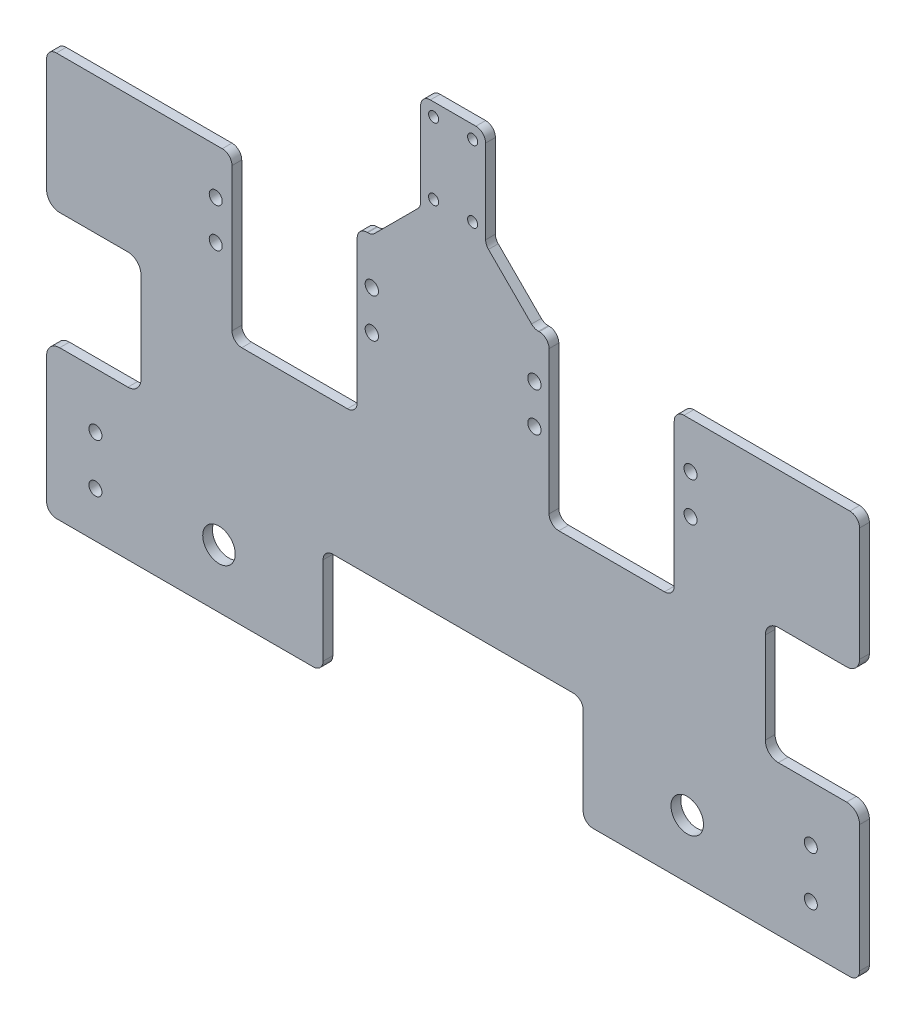
SolidWorks part; units mm, degrees
material "Thornel Mat VMA"
ref_plane "前视基准面" through (0, 0, 0) normal (0, 0, 1) x (1, 0, 0)
ref_plane "上视基准面" through (0, 0, 0) normal (0, 1, 0) x (1, 0, 0)
ref_plane "右视基准面" through (0, 0, 0) normal (1, 0, 0) x (0, 0, -1)
other "Configuration Table"
sketch "草图1" plane through (0, 0, 0) normal (0, 0, 1) x (1, 0, 0)
  line L0 (-32.5, 40) -> (-25, 40)
  line L1 (-25, 40) -> (-10, 55)
  line L2 (-10, 55) -> (-10, 85)
  line L3 (-10, 85) -> (10, 85)
  line L4 (-32.5, 40) -> (-32.5, 0)
  line L5 (-32.5, 0) -> (32.5, 0)
  line L6 (0, 0) -> (0, 50.9699) construction
  line L7 (32.5, 40) -> (32.5, 0)
  line L8 (10, 55) -> (10, 85)
  line L9 (25, 40) -> (10, 55)
  line L10 (32.5, 40) -> (25, 40)
  dimension "D1" = 65
  dimension "D2" = 85
  dimension "D3" = 30
  dimension "D4" = 40
  dimension "D5" = 50
  dimension "D6" = 20
extrude "凸台-拉伸1" add sketch "草图1" along normal blind 3
sketch "草图2" plane through (0, 0, 3) normal (0, 0, 1) x (1, 0, 0)
  line L0 (0, 85) -> (0, 65.679) construction
  line L1 (10, 85) -> (-10, 85) construction
  line L2 (-10, 70) -> (13.1812, 70) construction
  line L3 (-10, 85) -> (-10, 55) construction
  circle A0 centre (-6, 81) radius 1.55
  circle A2 centre (-6, 59) radius 1.55
  circle A3 centre (6, 59) radius 1.55
  circle A4 centre (6, 81) radius 1.55
  dimension "D1" = 4
  dimension "D2" = 4
  dimension "D3" = 3.1
extrude "切除-拉伸1" cut sketch "草图2" against normal through all
sketch "草图3" plane through (0, 0, 3) normal (0, 0, 1) x (1, 0, 0)
  line L0 (32.5, 20) -> (-48.6379, 20) construction
  line L1 (32.5, 0) -> (32.5, 40) construction
  line L2 (0, 0) -> (0, 100.1432) construction
  circle A0 centre (-25, 26) radius 2.05
  circle A2 centre (-25, 14) radius 2.05
  circle A3 centre (25, 14) radius 2.05
  circle A4 centre (25, 26) radius 2.05
  dimension "D1" = 12
  dimension "D2" = 50
  dimension "D3" = 4.1
extrude "切除-拉伸2" cut sketch "草图3" against normal through all
sketch "草图4" plane through (0, 0, 3) normal (0, 0, 1) x (1, 0, 0)
  line L0 (32.5, 0) -> (32.5, 40) construction
  line L1 (32.5, 40) -> (29.5, 40)
  line L2 (32.5, 40) -> (32.5, -0.4765)
  line L3 (32.5, -0.4765) -> (29.5, -0.4765)
  line L4 (29.5, 40) -> (29.5, -0.4765)
  line L5 (0, 85) -> (0, -21.7177) construction
  line L6 (10, 85) -> (-10, 85) construction
  line L7 (-29.5, 40) -> (-29.5, -0.4765)
  line L8 (-32.5, -0.4765) -> (-29.5, -0.4765)
  line L9 (-32.5, 40) -> (-32.5, -0.4765)
  line L10 (-32.5, 40) -> (-29.5, 40)
  dimension "D1" = 3
extrude "切除-拉伸3" cut sketch "草图4" against normal blind 10
sketch "草图5" plane through (0, 0, 3) normal (0, 0, 1) x (1, 0, 0)
  line L0 (0, 0) -> (0, -185.4243) construction
  line L1 (-125, -10) -> (125, -10)
  line L2 (0, 0) -> (0, -84)
  line L3 (-125, -84) -> (125, -84)
  line L4 (125, -10) -> (125, -84)
  line L5 (-125, -10) -> (-125, -84)
  line L6 (-68, -10) -> (-68, 40)
  line L7 (125, -10) -> (68, -10)
  line L8 (125, -10) -> (125, 40)
  line L9 (125, 40) -> (68, 40)
  line L10 (68, -10) -> (68, 40)
  line L11 (-125, 40) -> (-68, 40)
  line L12 (-125, -10) -> (-125, 40)
  line L13 (-125, -10) -> (-68, -10)
  line L14 (-125, -10) -> (-125, -84)
  line L16 (29.5, 40) -> (29.5, 0) construction
  line L17 (-29.5, 0) -> (29.5, 0)
  line L18 (-29.5, 0) -> (-29.5, -10)
  line L19 (-29.5, -10) -> (29.5, -10)
  line L20 (29.5, 0) -> (29.5, -10)
  line M16 (-29.5, 0) -> (29.5, 0)
  dimension "D1" = 250
  dimension "D2" = 50
  dimension "D3" = 68
  dimension "D4" = 74
  dimension "D5" = 10
extrude "凸台-拉伸2" add sketch "草图5" against normal blind 3 contours L10 L1 L8 L9 | L4 L1 L2 L3 | L1 L5 L3 L2 M16 | L12 L1 L6 L11 | L18 L1 L2 M16 | L20 L2 L1 M16 region at (-96.5, 15, 3) region at (-62.5, -47, 3) region at (-14.75, -5, 3) region at (62.5, -47, 3) region at (14.75, -5, 3) region at (96.5, 15, 3)
sketch "草图6" plane through (0, 0, 3) normal (0, 0, 1) x (1, 0, 0)
  line L0 (0, 0) -> (0, -103.0936) construction
  line L1 (-125, -84) -> (125, -84) construction
  line L2 (-40, -84) -> (40, -84)
  line L3 (0, -84) -> (0, -51)
  line L4 (-40, -51) -> (40, -51)
  line L5 (40, -84) -> (40, -51)
  line L6 (-40, -84) -> (-40, -51)
  line M14 (-125, -84) -> (125, -84)
  dimension "D1" = 40
  dimension "D2" = 33
extrude "切除-拉伸4" cut sketch "草图6" against normal blind 4 contours L2 L5 L4 L3 | L6 L3 L4 M14 region at (-20, -67.5, 3) region at (20, -67.5, 3)
fillet "圆角1" radius 3 22 edges at (-40, -51, 1.5) (40, -51, 1.5) (40, -84, 1.5) (125, -84, 1.5) (68, 40, 1.5) (68, -10, 1.5) (29.5, -10, 1.5) (29.5, 40, 1.5) (25, 40, 1.5) (10, 55, 1.5) (10, 85, 1.5) (-10, 85, 1.5) (-10, 55, 1.5) (-25, 40, 1.5) (-29.5, 40, 1.5) (-29.5, -10, 1.5) (-68, -10, 1.5) (-68, 40, 1.5) (-125, 40, 1.5) (-125, -84, 1.5) (-40, -84, 1.5) (125, 40, 1.5)
sketch "草图7" plane through (0, 0, 3) normal (0, 0, 1) x (1, 0, 0)
  line L0 (125, -81) -> (125, 37) construction
  line L1 (43, -84) -> (122, -84) construction
  line L2 (0, 0) -> (0, -96.374) construction
  line L3 (122, 40) -> (71, 40) construction
  line L4 (96, -2) -> (127, -2)
  line L5 (96, -2) -> (96, -38)
  line L6 (96, -38) -> (127, -38)
  line L7 (127, -2) -> (127, -38)
  line L8 (-127, -2) -> (-127, -38)
  line L9 (-96, -38) -> (-127, -38)
  line L10 (-96, -2) -> (-96, -38)
  line L11 (-96, -2) -> (-127, -2)
  circle A0 centre (72, -66) radius 5
  circle A1 centre (-72, -66) radius 5
  dimension "D1" = 53
  dimension "D2" = 10
  dimension "D3" = 18
  dimension "D4" = 42
  dimension "D5" = 29
  dimension "D6" = 36
  dimension "D7" = 31
extrude "切除-拉伸5" cut sketch "草图7" against normal blind 4
sketch "草图8" plane through (0, 0, 3) normal (0, 0, 1) x (1, 0, 0)
  line L0 (0, 95.4541) -> (0, -92.5342) construction
  line L1 (122, 40) -> (71, 40) construction
  line L2 (125, -2) -> (125, 37) construction
  circle A0 centre (73, 26) radius 2
  circle A1 centre (73, 14) radius 2
  circle A2 centre (-73, 14) radius 2
  circle A3 centre (-73, 26) radius 2
  dimension "D1" = 4
  dimension "D2" = 4
  dimension "D3" = 12
  dimension "D4" = 14
  dimension "D5" = 52
  dimension "D6" = 52
extrude "切除-拉伸6" cut sketch "草图8" against normal blind 4
sketch "草图9" plane through (0, 0, 3) normal (0, 0, 1) x (1, 0, 0)
  line L1 (125, -81) -> (125, -38) construction
  line L2 (0, 116.3395) -> (0, -160.2335) construction
  line L3 (43, -84) -> (122, -84) construction
  circle A0 centre (110, -55) radius 2
  circle A1 centre (110, -70) radius 2
  circle A2 centre (-110, -70) radius 2
  circle A3 centre (-110, -55) radius 2
  dimension "D1" = 4
  dimension "D2" = 4
  dimension "D3" = 15
  dimension "D4" = 14
  dimension "D5" = 15
  dimension "D6" = 15
extrude "切除-拉伸7" cut sketch "草图9" against normal blind 4
fillet "圆角2" radius 4 8 edges at (-96, -38, 1.5) (-125, -38, 1.5) (125, -38, 1.5) (96, -38, 1.5) (125, -2, 1.5) (-125, -2, 1.5) (-96, -2, 1.5) (96, -2, 1.5)
